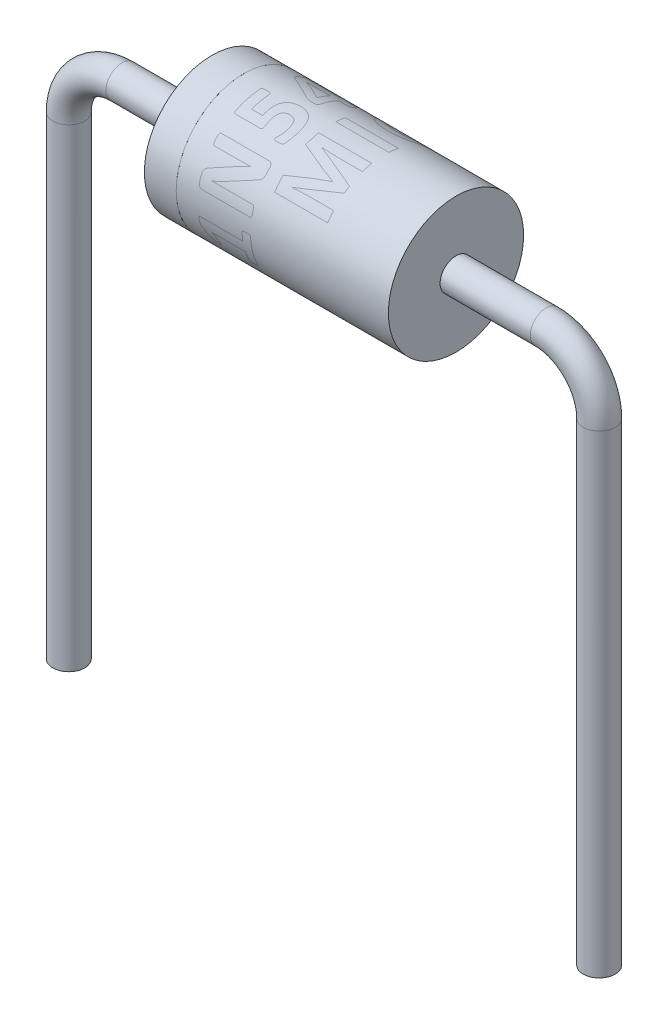
SolidWorks part; units mm, degrees
other "Wire"
other "Cathode Silver Band"
other "Diode"
ref_plane "Front Plane" through (0, 0, 0) normal (0, 0, 1) x (1, 0, 0)
ref_plane "Top Plane" through (0, 0, 0) normal (0, 1, 0) x (1, 0, 0)
ref_plane "Right Plane" through (0, 0, 0) normal (1, 0, 0) x (0, 0, -1)
sketch "Sketch1" plane through (0, 0, 0) normal (1, 0, 0) x (0, 0, -1)
  circle A0 centre (0, 0) radius 2.55
  circle A1 centre (0, 0) radius 0.6
  dimension "D1" = 5.1
  dimension "D2" = 1.2
extrude "Boss-Extrude1" add sketch "Sketch1" along normal mid plane 9.2
sketch "Sketch2" plane through (-4.6, 0, 0) normal (-1, 0, 0) x (0, 0, 1)
  circle A1 centre (0, 0) radius 2.55 construction
  circle A2 centre (0, 0) radius 2.54
  circle A3 centre (0, 0) radius 2.54
  circle A4 centre (0, 0) radius 2.55
  dimension "D1" = 0.01
extrude "Cut-Extrude1" cut sketch "Sketch2" against normal blind 1.2
sketch "Sketch3" plane through (-3.4, 0, 0) normal (-1, 0, 0) x (0, 0, 1)
  circle A0 centre (0, 0) radius 2.54 construction
  circle A1 centre (0, 0) radius 2.54
  circle A2 centre (0, 0) radius 2.55 construction
  circle A3 centre (0, 0) radius 2.55
extrude "Boss-Extrude2" add sketch "Sketch3" along normal up to surface (1.2 mm away) separate body up to face at (-4.6, 0, -0.6)
ref_plane "Plane1" through (0, 5, 0) normal (0, 1, 0) x (1, 0, 0)
sketch "Sketch4" plane through (0, 5, 0) normal (0, 1, 0) x (1, 0, 0)
  line L0 (-0.6, 7.5) -> (-0.6, -7.5) construction
  line L1 (-0.6, 0) -> (-4.6, 0) construction
  line L2 (-4.6, 2.55) -> (-4.6, -2.55) construction
  line L4 (-0.6, 0) -> (1.9, 0) construction
  line L5 (1.9, 7.5) -> (1.9, -7.5) construction
  text T0 "1N5404" font "Calibri" height 2
  text T1 "MIC" font "Corbel" height 2
  dimension "D1" = 4
  dimension "D2" = 15
  dimension "D3" = 2.5
wrap "Wrap1" sketch "Sketch4" wrap type scribe source sketch "Sketch4" face at (4.6, 0, -2.55)
sketch "Sketch5" plane through (0, 0, 0) normal (0, 0, 1) x (1, 0, 0)
  line L0 (0, 0) -> (-8, 0)
  line L1 (-10, -2) -> (-10, -19.8584)
  line L2 (0, 0) -> (8, 0)
  line L3 (10, -2) -> (10, -19.8584)
  arc A0 (-8, 0) -> (-10, -2) centre (-8, -2) ccw
  arc A1 (8, 0) -> (10, -2) centre (8, -2) cw
  dimension "D2" = 2
  dimension "D3" = 58
  dimension "D1" = 20
sketch "Sketch6" plane through (0, 0, 0) normal (1, 0, 0) x (0, 0, -1)
  circle A0 centre (0, 0) radius 0.6
  dimension "D1" = 1.2
sweep "Sweep1" add profiles "Sketch6" path "Sketch5"
